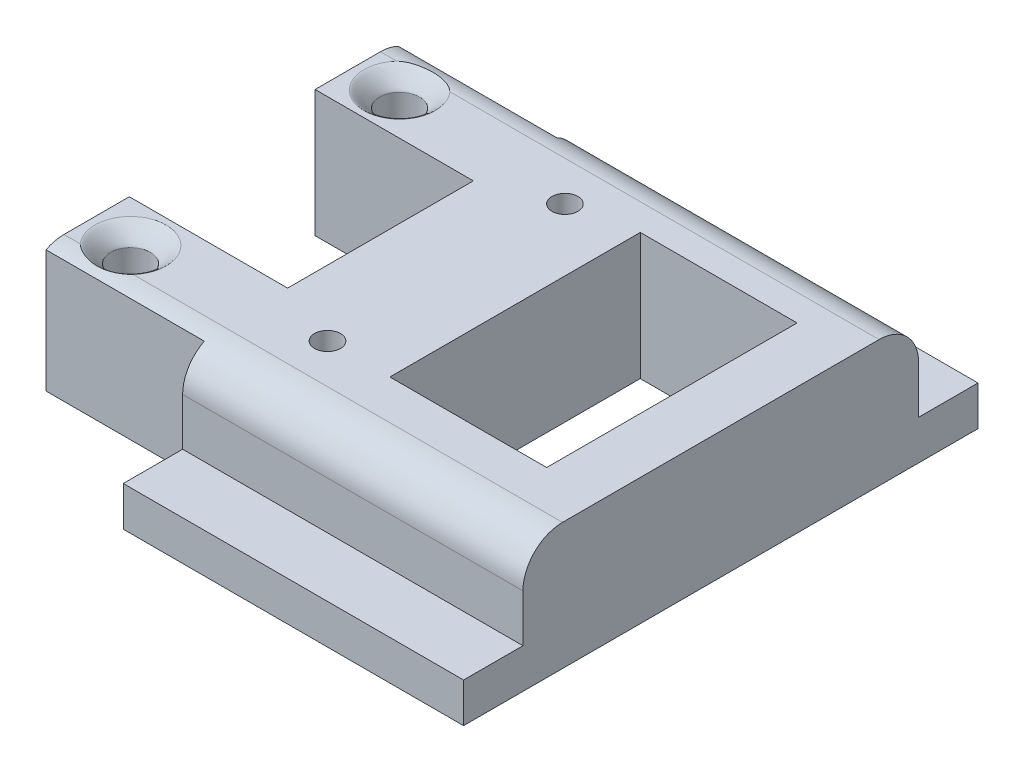
SolidWorks part; units mm, degrees
ref_plane "Front Plane" through (0, 0, 0) normal (0, 0, 1) x (1, 0, 0)
ref_plane "Top Plane" through (0, 0, 0) normal (0, 1, 0) x (1, 0, 0)
ref_plane "Right Plane" through (0, 0, 0) normal (1, 0, 0) x (0, 0, -1)
sketch "Sketch1" plane through (0, 0, 0) normal (1, 0, 0) x (0, 0, -1)
  line L0 (0, 0) -> (-50, 0) construction
  line L1 (-50, 0) -> (0, 0)
  line L2 (0, 0) -> (0, -11)
  line L3 (0, -11) -> (7.5, -11)
  line L4 (-50, 0) -> (-50, -11)
  line L5 (-50, -11) -> (-57.5, -11)
  line L6 (7.5, -11) -> (7.5, -16)
  line L7 (-57.5, -11) -> (-57.5, -16)
  line L8 (-57.5, -16) -> (7.5, -16)
  dimension "D1" = 50
  dimension "D2" = 11
  dimension "D3" = 7.5
  dimension "D4" = 5
extrude "Boss-Extrude1" add sketch "Sketch1" along normal blind 43
sketch "Sketch8" plane through (0, 0, 0) normal (0, 1, 0) x (1, 0, 0)
  line L0 (43, -25) -> (0, -25) construction
  line L1 (43, 0) -> (43, -50) construction
  line L2 (0, 0) -> (0, -50) construction
  line L3 (8.3074, -25) -> (8.3074, -10) construction
  line L4 (8.3074, -25) -> (8.3074, -40) construction
  line L5 (9.9457, -10) -> (41.2508, -10) construction
  circle A0 centre (8.3074, -40) radius 1.6383
  circle A1 centre (8.3074, -10) radius 1.6383
  point P9 (8.3074, -25)
  dimension "D3" = 3.2766
  dimension "D4" = 3.2766
  dimension "D1" = 15
  dimension "D2" = 15
extrude "Cut-Extrude6" cut sketch "Sketch8" against normal through all both and the other way through all
sketch "Sketch15" plane through (0, 0, 0) normal (-1, 0, 0) x (0, 0, 1)
  line L0 (25, 0) -> (25, -16) construction
  line L1 (0, 0) -> (50, 0) construction
  line L2 (57.5, -16) -> (-7.5, -16) construction
  line L3 (47.2641, 0) -> (36.7359, 0)
  line L4 (2.7359, -16) -> (13.2641, -16)
  line L5 (2.7359, -16) -> (2.7359, 0)
  line L6 (2.7359, 0) -> (13.2641, 0)
  line L7 (13.2641, -16) -> (13.2641, 0)
  line L8 (19.7359, -16) -> (30.2641, 0) construction
  line L9 (19.7359, 0) -> (30.2641, -16) construction
  line L10 (36.7359, -16) -> (36.7359, 0)
  line L11 (47.2641, -16) -> (36.7359, -16)
  line L12 (47.2641, -16) -> (47.2641, 0)
  point P6 (25, -8)
extrude "Boss-Extrude2" add sketch "Sketch15" along normal blind 20
sketch "Sketch16" plane through (0, 0, 0) normal (0, 1, 0) x (1, 0, 0)
  line L0 (-20, -8) -> (0, -8) construction
  line L1 (-20, -13.2641) -> (-20, -2.7359) construction
  line L2 (0, -25) -> (5.9831, -25) construction
  line L3 (0, -13.2641) -> (0, -36.7359) construction
  circle A0 centre (-14.5853, -8) radius 2.5
  circle A1 centre (-14.5853, -42) radius 2.5
  dimension "D1" = 5
extrude "Cut-Extrude7" cut sketch "Sketch16" against normal through all both and the other way through all
fillet "Fillet5" radius 2 1 edges at (-14.5853, 0, 5.5) conic radius 10
sketch "Sketch17" plane through (0, 0, 0) normal (0, 1, 0) x (1, 0, 0)
  line L0 (6.6691, -10) -> (-8.8309, -10) construction
  circle A1 centre (8.3074, -10) radius 1.6383 construction
  dimension "D1" = 15.5
fillet "Fillet6" radius 2 1 edges at (-14.5853, 0, 39.5) conic radius 10
sketch "Sketch19" plane through (0, -16, 0) normal (0, -1, 0) x (1, 0, 0)
  line L0 (0, 57.5) -> (-20.8218, 57.5) construction
  line L1 (-14.5853, 42) -> (-14.5853, 57.5) construction
sketch "Sketch20" plane through (0, -16, 0) normal (0, -1, 0) x (1, 0, 0)
  line L0 (0, 25) -> (43, 25) construction
  line L1 (13.5036, 10) -> (10.9055, 14.5)
  line L2 (10.9055, 14.5) -> (5.7094, 14.5)
  line L3 (5.7094, 14.5) -> (3.1113, 10)
  line L4 (3.1113, 10) -> (5.7094, 5.5)
  line L5 (5.7094, 5.5) -> (10.9055, 5.5)
  line L6 (10.9055, 5.5) -> (13.5036, 10)
  line L7 (0, 36.7359) -> (0, 13.2641) construction
  line L8 (43, 57.5) -> (43, -7.5) construction
  line L9 (10.9055, 44.5) -> (13.5036, 40)
  line L10 (5.7094, 44.5) -> (10.9055, 44.5)
  line L11 (3.1113, 40) -> (5.7094, 44.5)
  line L12 (5.7094, 35.5) -> (3.1113, 40)
  line L13 (10.9055, 35.5) -> (5.7094, 35.5)
  line L14 (13.5036, 40) -> (10.9055, 35.5)
  circle A0 centre (8.3074, 10) radius 4.5 construction
  dimension "D1" = 9
extrude "Cut-Extrude8" cut sketch "Sketch20" against normal blind 3.5
fillet "Fillet7" radius 0.5 6 edges at (8.3074, -16, 5.5) (12.2046, -16, 7.75) (12.2046, -16, 12.25) (8.3074, -16, 14.5) (4.4103, -16, 7.75) (4.4103, -16, 12.25)
fillet "Fillet8" radius 0.5 6 edges at (8.3074, -16, 35.5) (12.2046, -16, 37.75) (12.2046, -16, 42.25) (4.4103, -16, 37.75) (4.4103, -16, 42.25) (8.3074, -16, 44.5)
sketch "Sketch21" plane through (0, 0, 0) normal (0, 1, 0) x (1, 0, 0)
  line L0 (0, -25) -> (43, -25) construction
  line L1 (0, -13.2641) -> (0, -36.7359) construction
  line L2 (43, 0) -> (43, -50) construction
  line L3 (16.1862, -25) -> (16.1862, -8.3617)
  line L4 (16.1862, -8.3617) -> (36, -8.3617)
  line L5 (36, -8.3617) -> (36, -40)
  line L6 (36, -40) -> (16.1862, -40)
  line L7 (16.1862, -40) -> (16.1862, -25)
  dimension "D1" = 7
extrude "Cut-Extrude9" cut sketch "Sketch21" against normal through all both and the other way through all
fillet "Fillet9" radius 5 2 edges at (21.5, 0, 50) (21.5, 0, 0)
